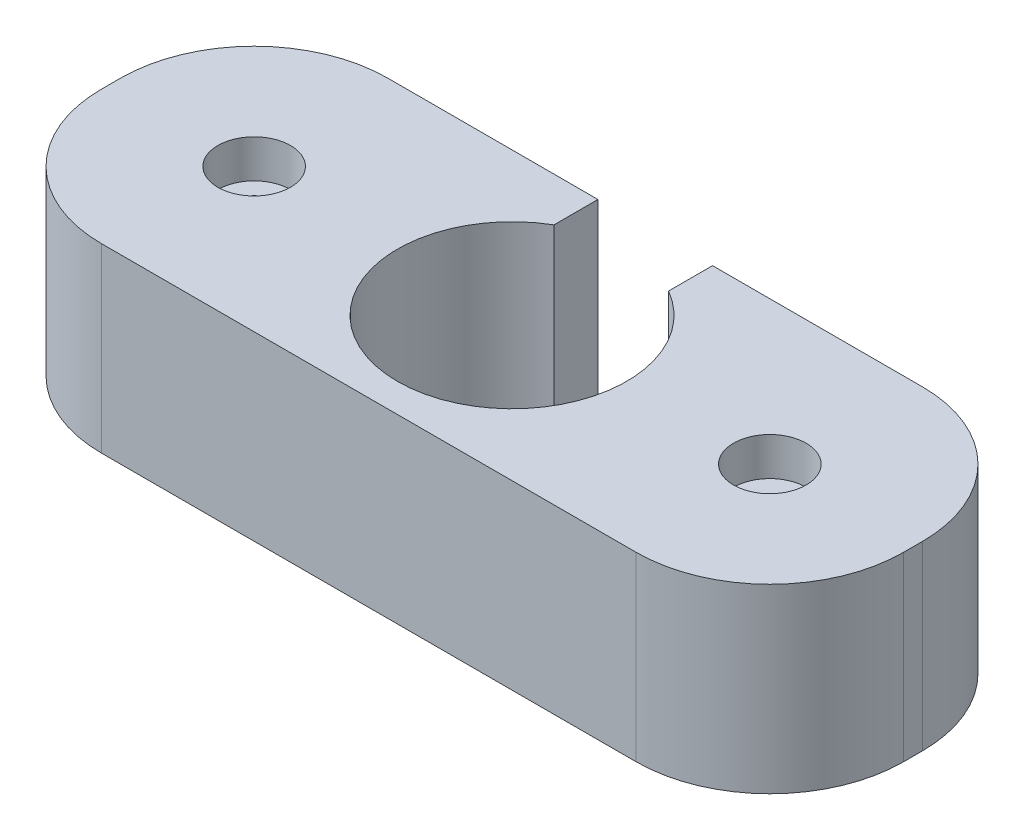
SolidWorks part; units mm, degrees
ref_plane "Front Plane" through (0, 0, 0) normal (0, 0, 1) x (1, 0, 0)
ref_plane "Top Plane" through (0, 0, 0) normal (0, 1, 0) x (1, 0, 0)
ref_plane "Right Plane" through (0, 0, 0) normal (1, 0, 0) x (0, 0, -1)
sketch "Sketch1" plane through (0, 0, 0) normal (0, 1, 0) x (1, 0, 0)
  line L1 (0, 0) -> (42, 0)
  line L2 (0, 0) -> (0, 15)
  line L3 (0, 15) -> (42, 15)
  line L4 (42, 0) -> (42, 15)
  dimension "D1" = 42
  dimension "D2" = 15
extrude "Boss-Extrude1" add sketch "Sketch1" against normal blind 9.5
sketch "Sketch2" plane through (0, 0, 0) normal (0, 1, 0) x (1, 0, 0)
  line L2 (0, 15) -> (0, 0) construction
  line L3 (42, 15) -> (0, 15) construction
  circle A0 centre (21, 7.5) radius 6
  point P4 (0, 7.5)
  point P7 (21, 15)
  dimension "D2" = 12
extrude "Cut-Extrude1" cut sketch "Sketch2" against normal up to next
sketch "Sketch4" plane through (0, 0, 0) normal (0, 1, 0) x (1, 0, 0)
  line L0 (21, 15) -> (21, 0) construction
  line L1 (7.5, 7.5) -> (34.5, 7.5) construction
  line L2 (42, 15) -> (0, 15) construction
  line L3 (0, 0) -> (42, 0) construction
  circle A0 centre (7.5, 7.5) radius 1.9
  circle A1 centre (34.5, 7.5) radius 1.9
  point P6 (21, 7.5)
  point P11 (21, 7.5)
  dimension "D3" = 3.8
  dimension "D1" = 27
extrude "Cut-Extrude3" cut sketch "Sketch4" against normal blind 2
sketch "Sketch5" plane through (0, -9.5, 0) normal (0, -1, 0) x (-1, 0, 0)
  line L3 (-34.5, 7.5) -> (-7.5, 7.5) construction
  line L4 (-21, 15) -> (-21, 0) construction
  line L5 (-42, 15) -> (0, 15) construction
  line L6 (0, 0) -> (-42, 0) construction
  circle A0 centre (-34.5, 7.5) radius 2.05
  circle A1 centre (-7.5, 7.5) radius 2.05
  point P4 (-21, 7.5)
  point P5 (-21, 7.5)
  dimension "D5" = 4.1
  dimension "D6" = 27
extrude "Cut-Extrude4" cut sketch "Sketch5" against normal blind 5
sketch "Sketch6" plane through (0, -2, 0) normal (0, 1, 0) x (1, 0, 0)
  circle A1 centre (7.5, 7.5) radius 0.95
  circle A2 centre (34.5, 7.5) radius 0.95
  circle A3 centre (7.5, 7.5) radius 1.9 construction
  circle A4 centre (34.5, 7.5) radius 1.9 construction
  dimension "D1" = 1.9
extrude "Cut-Extrude5" cut sketch "Sketch6" against normal blind 3
fillet "Fillet1" radius 7 4 edges at (42, -4.75, -15) (0, -4.75, -15) (42, -4.75, 0) (0, -4.75, 0)
sketch "Sketch7" plane through (0, 0, -15) normal (0, 0, -1) x (-1, 0, 0)
  line L0 (-35, 0) -> (-7, 0) construction
  line L1 (-35, -9.5) -> (-7, -9.5) construction
  line L2 (-24, 0) -> (-18, 0)
  line L3 (-24, 0) -> (-24, -9.5)
  line L4 (-24, -9.5) -> (-18, -9.5)
  line L5 (-18, 0) -> (-18, -9.5)
  line L6 (-7, -4.75) -> (-18, -4.75) construction
  line L7 (-7, -9.5) -> (-7, 0) construction
  line L8 (-24, -4.75) -> (-35, -4.75) construction
  line L9 (-35, 0) -> (-35, -9.5) construction
  dimension "D1" = 11
extrude "Cut-Extrude6" cut sketch "Sketch7" against normal blind 3
